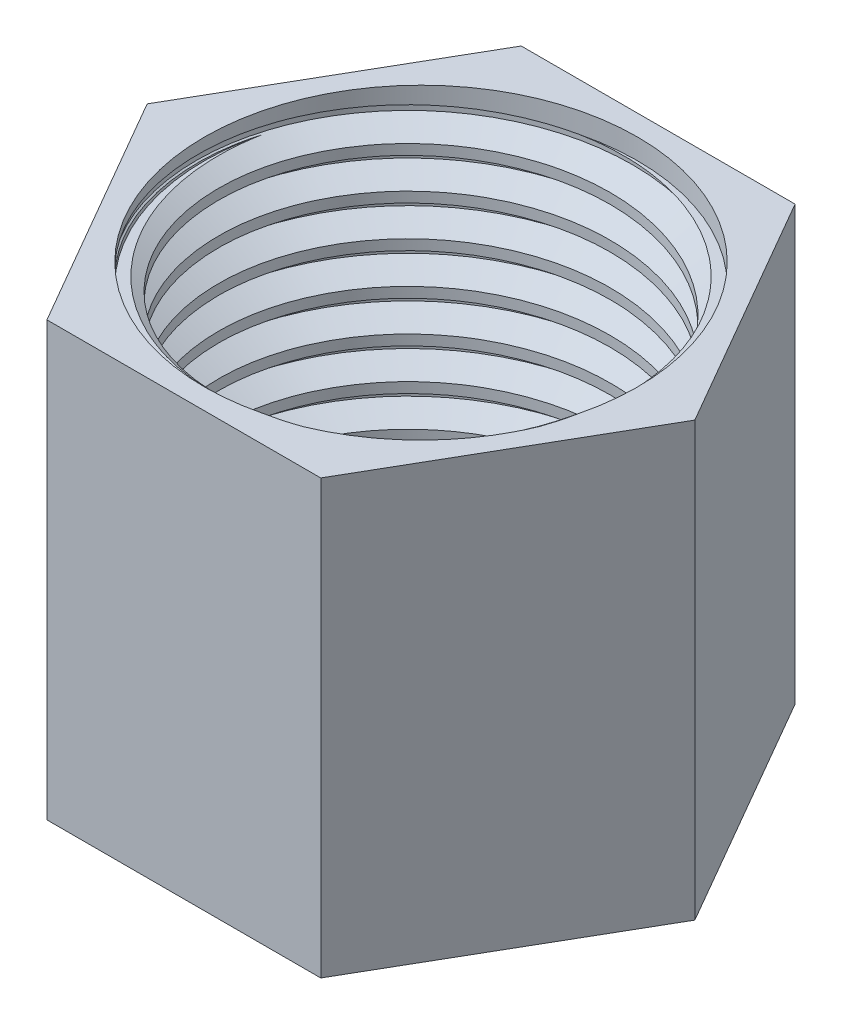
SolidWorks part; units mm, degrees
ref_plane "Plan de face" through (0, 0, 0) normal (0, 0, 1) x (1, 0, 0)
ref_plane "Plan de dessus" through (0, 0, 0) normal (0, 1, 0) x (1, 0, 0)
ref_plane "Plan de droite" through (0, 0, 0) normal (1, 0, 0) x (0, 0, -1)
sketch "Esquisse1" plane through (0, 0, 0) normal (0, 1, 0) x (1, 0, 0)
  line L1 (-6.6395, -11.5) -> (6.6395, -11.5)
  line L2 (6.6395, -11.5) -> (13.2791, 0)
  line L3 (13.2791, 0) -> (6.6395, 11.5)
  line L4 (6.6395, 11.5) -> (-6.6395, 11.5)
  line L5 (-6.6395, 11.5) -> (-13.2791, 0)
  line L6 (-13.2791, 0) -> (-6.6395, -11.5)
  circle A0 centre (0, 0) radius 11.5 construction
  circle A1 centre (0, 0) radius 9.5
  dimension "D2" = 19
  dimension "D1" = 23
extrude "Boss.-Extru.1" add sketch "Esquisse1" along normal blind 21
thread "Filetage1" pitch 2 method cut trim with start face yes trim with end face yes profile "Profil de filetage1" start angle 0, offset 2, length 0, pitch 2, diameter 19
ref_plane "Plan1" through (-9.5, 23, 0) normal (0, 0, 1) x (-1, 0, 0)
sketch "Profil de filetage1" plane through (-9.5, 23, 0) normal (0, 0, 1) x (-1, 0, 0)
  line L0 (0, 0) -> (0, 2) construction
  line L1 (0, 0) -> (1.0825, 0.625)
  line L2 (1.0825, 0.625) -> (1.0825, 0.875)
  line L3 (1.0825, 0.875) -> (0, 1.5)
  line L4 (1.0825, 0.75) -> (0, 0.75) construction
  line L11 (0, 0) -> (0, 1.5)
  point P2 (0, 0)
  dimension "Pitch" = 2
  dimension "Profile_Angle" = 60
  dimension "Profile_Land" = 0.25
  dimension "Profile_Height" = 1.0825
sketch "Esquisse2" plane through (0, 21, 0) normal (0, 1, 0) x (1, 0, 0)
  circle A0 centre (0, 0) radius 10.5
  dimension "D1" = 21
extrude "Enlèv. mat.-Extru.1" cut sketch "Esquisse2" against normal blind 1
